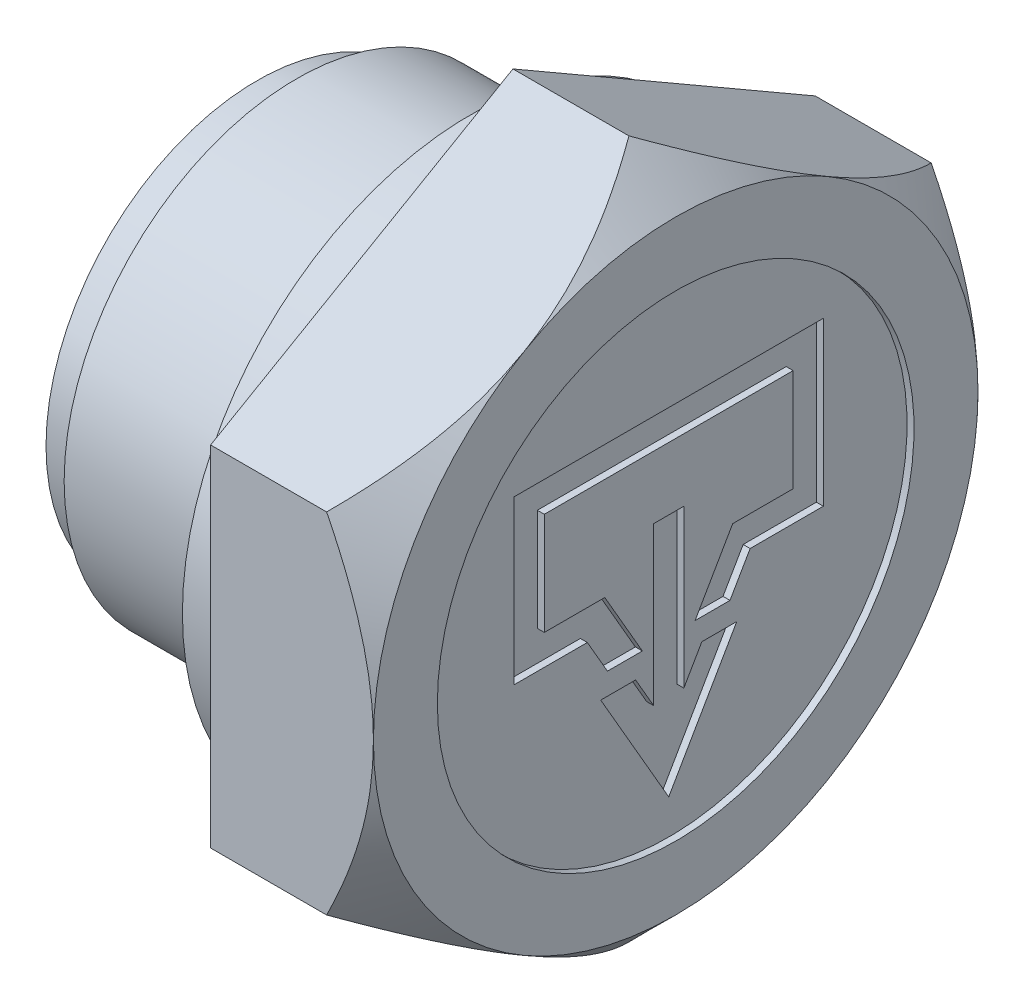
SolidWorks part; units mm, degrees
ref_plane "Piano frontale" through (0, 0, 0) normal (0, 0, 1) x (1, 0, 0)
ref_plane "Piano superiore" through (0, 0, 0) normal (0, 1, 0) x (1, 0, 0)
ref_plane "Piano destro" through (0, 0, 0) normal (1, 0, 0) x (0, 0, -1)
ref_plane "Piano1" through (0, 0, 0) normal (0, 0, 1) x (1, 0, 0)
sketch "Schizzo1" plane through (0, 0, 0) normal (0, 0, 1) x (1, 0, 0)
  line L0 (14.2, 0) -> (14.2, 5.6879)
  line L1 (13.7174, 6.1876) -> (0, 6.6667)
  line L2 (0, 6.6667) -> (0, 9.0798)
  line L3 (0, 9.0798) -> (1.7, 9.0798)
  line L4 (1.7, 9.0798) -> (1.7, 10)
  line L5 (1.7, 10) -> (9.1667, 10)
  line L6 (9.1667, 10) -> (9.1667, 12.381)
  line L7 (9.1667, 12.381) -> (11, 12.381)
  line L8 (11, 12.381) -> (11, 20)
  line L9 (11, 20) -> (18, 13)
  line L10 (18, 13) -> (18, 10.25)
  line L11 (18, 10.25) -> (17.7, 10.25)
  line L12 (17.7, 10.25) -> (17.7, 0)
  line L13 (17.7, 0) -> (14.2, 0)
  line L14 (18, 0) -> (0, 0) construction
  arc A0 (14.2, 5.6879) -> (13.7174, 6.1876) centre (13.7, 5.6879) ccw
revolve "Rivoluzione1" add sketch "Schizzo1" angle 360 about L14 reverse direction yes
cosmetic thread "Filettatura cosmetica1" parameters "D1"=7.4667, "D2"=18.16
ref_plane "Piano2" through (17.7, 0, 0) normal (1, 0, 0) x (0, 0, -1)
sketch "Schizzo2" plane through (17.7, 0, 0) normal (1, 0, 0) x (0, 0, -1)
  line L0 (-6.65, 5.75) -> (-6.65, -1.25)
  line L1 (-6.65, -1.25) -> (-3.5006, -1.25)
  line L2 (-3.5006, -1.25) -> (-2.6345, -2.75)
  line L3 (-2.6345, -2.75) -> (-1.1334, -2.75)
  line L4 (-1.1334, -2.75) -> (-2.75, 0.05)
  line L5 (-2.75, 0.05) -> (-5.35, 0.05)
  line L6 (-5.35, 0.05) -> (-5.35, 4.45)
  line L7 (-5.35, 4.45) -> (5.35, 4.45)
  line L8 (5.35, 4.45) -> (5.35, 0.05)
  line L9 (5.35, 0.05) -> (2.75, 0.05)
  line L10 (2.75, 0.05) -> (1.1334, -2.75)
  line L11 (1.1334, -2.75) -> (2.6345, -2.75)
  line L12 (2.6345, -2.75) -> (3.5006, -1.25)
  line L13 (3.5006, -1.25) -> (6.65, -1.25)
  line L14 (6.65, -1.25) -> (6.65, 5.75)
  line L15 (6.65, 5.75) -> (-6.65, 5.75)
extrude "Taglio-Estrusione1" cut sketch "Schizzo2" against normal blind 0.3 and the other way blind 0.3
ref_plane "Piano3" through (17.7, 0, 0) normal (1, 0, 0) x (0, 0, -1)
sketch "Schizzo3" plane through (17.7, 0, 0) normal (1, 0, 0) x (0, 0, -1)
  line L0 (-2.925, -3.6837) -> (0, -8.75)
  line L1 (0, -8.75) -> (2.925, -3.6837)
  line L2 (2.925, -3.6837) -> (1.4239, -3.6837)
  line L3 (1.4239, -3.6837) -> (0.65, -5.0242)
  line L4 (0.65, -5.0242) -> (0.65, 1.75)
  line L5 (0.65, 1.75) -> (-0.65, 1.75)
  line L6 (-0.65, 1.75) -> (-0.65, -5.0242)
  line L7 (-0.65, -5.0242) -> (-1.4239, -3.6837)
  line L8 (-1.4239, -3.6837) -> (-2.925, -3.6837)
extrude "Taglio-Estrusione2" cut sketch "Schizzo3" against normal blind 0.3 and the other way blind 0.3
ref_plane "Piano4" through (17.7, 0, 0) normal (1, 0, 0) x (0, 0, -1)
sketch "Schizzo4" plane through (17.7, 0, 0) normal (1, 0, 0) x (0, 0, -1)
  line L0 (-26, -15.0111) -> (0, -30.0222)
  line L1 (0, -30.0222) -> (26, -15.0111)
  line L2 (26, -15.0111) -> (26, 15.0111)
  line L3 (26, 15.0111) -> (0, 30.0222)
  line L4 (0, 30.0222) -> (-26, 15.0111)
  line L5 (-26, 15.0111) -> (-26, -15.0111)
  line L6 (-13, -7.5056) -> (0, -15.0111)
  line L7 (0, -15.0111) -> (13, -7.5056)
  line L8 (13, -7.5056) -> (13, 7.5056)
  line L9 (13, 7.5056) -> (0, 15.0111)
  line L10 (0, 15.0111) -> (-13, 7.5056)
  line L11 (-13, 7.5056) -> (-13, -7.5056)
extrude "Taglio-Estrusione3" cut sketch "Schizzo4" against normal blind 10.701 and the other way blind 10.701
